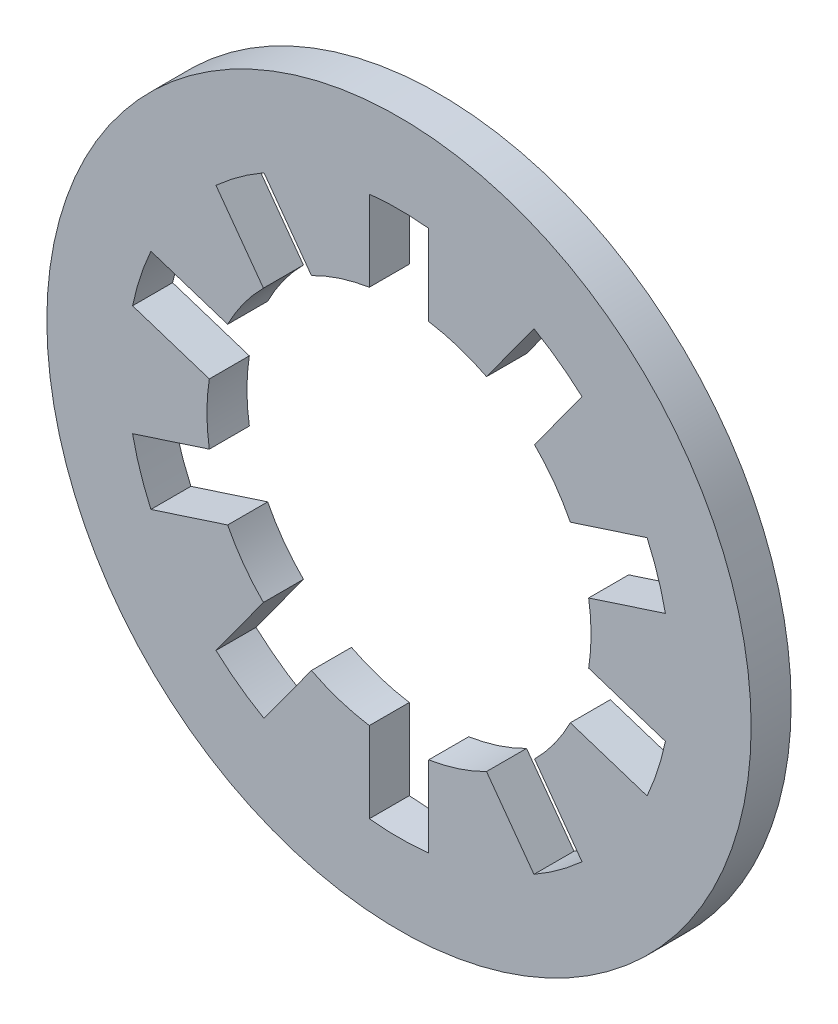
SolidWorks part; units mm, degrees
ref_plane "Front Plane" through (0, 0, 0) normal (0, 0, 1) x (1, 0, 0)
ref_plane "Top Plane" through (0, 0, 0) normal (0, 1, 0) x (1, 0, 0)
ref_plane "Right Plane" through (0, 0, 0) normal (1, 0, 0) x (0, 0, -1)
sketch "Sketch1" plane through (0, 0, 0) normal (0, 0, 1) x (1, 0, 0)
  circle A0 centre (0, 0) radius 2.2
  circle A1 centre (0, 0) radius 1.2
extrude "Extrude1" add sketch "Sketch1" along normal blind 0.25
sketch "Sketch2" plane through (0, 0, 0) normal (0, 0, 1) x (1, 0, 0)
  line L0 (0, 0) -> (0.5253, 1.6168) construction
  line L1 (0, 0) -> (0, 1.7) construction
  line L2 (0, 0) -> (-0.5253, 1.6168) construction
  line L3 (-0.3708, 1.1413) -> (0, 1.1413) construction
  line L4 (-0.1854, 1.6899) -> (-0.1854, 1.1856)
  line L5 (0.1854, 1.6899) -> (0.1854, 1.1856)
  line L6 (-0.1854, 1.1856) -> (0.1854, 1.1856)
  circle A0 centre (0, 0) radius 1.2 construction
  circle A1 centre (0, 0) radius 1.2 construction
  arc A2 (0.1854, 1.6899) -> (-0.1854, 1.6899) centre (0, 0) ccw
  dimension "D1" = 3.4
  dimension "D2" = 18
  dimension "D3" = 18
extrude "Cut-Extrude1" cut sketch "Sketch2" along normal through all
pattern_circular "CirPattern1" count 10 over 360 of "Cut-Extrude1"
sketch "Sketch3" plane through (0, 0, 0) normal (0, 0, 1) x (1, 0, 0)
  line L0 (0, 0) -> (0, 1.7) construction
  line L1 (0, 0) -> (0.5814, 1.5975) construction
  line L2 (0, 0) -> (-0.5814, 1.5975) construction
  line L3 (-0.4104, 1.1276) -> (0, 1.1276) construction
  line L4 (0.2052, 1.6876) -> (0.2052, 1.1823)
  line L5 (-0.2052, 1.6876) -> (-0.2052, 1.1823)
  line L6 (-0.2052, 1.1823) -> (0.2052, 1.1823)
  circle A0 centre (0, 0) radius 1.2 construction
  circle A1 centre (0, 0) radius 1.2 construction
  arc A2 (0.2052, 1.6876) -> (-0.2052, 1.6876) centre (0, 0) ccw
  circle A3 centre (0, 0) radius 1.2 construction
  dimension "D1" = 3.4
  dimension "D2" = 20
  dimension "D3" = 20
extrude "Cut-Extrude2" [suppressed] cut sketch "Sketch3" along normal through all
pattern_circular "CirPattern2" [suppressed] count 9 over 360 of bodies 104
equation "\"D1@Sketch2\" =  ( \"A@Sketch1\" + \"B@Sketch1\" )  / 2"
equation "\"D1@Sketch3\" =  ( \"A@Sketch1\" + \"B@Sketch1\" )  / 2"
